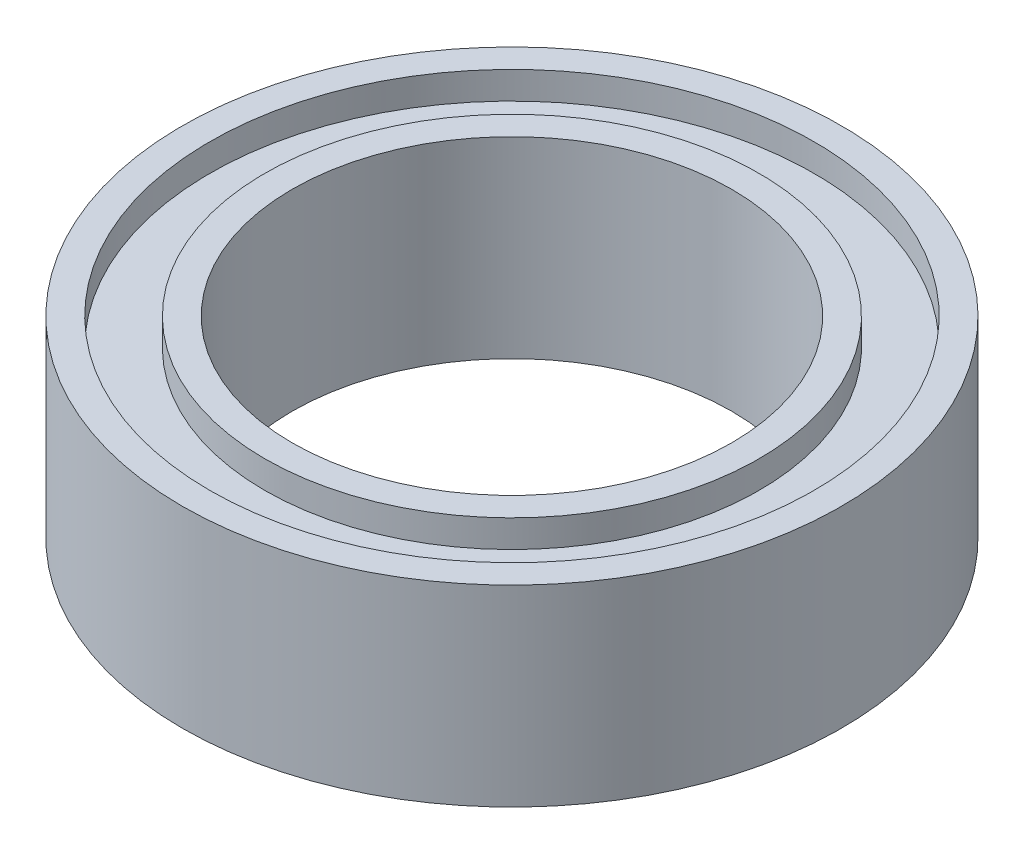
SolidWorks part; units mm, degrees
ref_plane "前视基准面" through (0, 0, 0) normal (0, 0, 1) x (1, 0, 0)
ref_plane "上视基准面" through (0, 0, 0) normal (0, 1, 0) x (1, 0, 0)
ref_plane "右视基准面" through (0, 0, 0) normal (1, 0, 0) x (0, 0, -1)
sketch "草图1" plane through (0, 0, 0) normal (0, 1, 0) x (1, 0, 0)
  circle A0 centre (0, 0) radius 4
  circle A1 centre (0, 0) radius 4.5
  circle A2 centre (0, 0) radius 5.5
  circle A3 centre (0, 0) radius 6
  dimension "D1" = 8
  dimension "D2" = 9
  dimension "D3" = 11
  dimension "D4" = 12
extrude "凸台-拉伸1" add sketch "草图1" along normal blind 3.5 contours A0 | A1
extrude "凸台-拉伸2" add sketch "草图1<3>" along normal blind 3 contours A1 | A2
sketch "草图1<3>" plane through (0, 0, 0) normal (0, 1, 0) x (1, 0, 0) same geometry as "草图1"
extrude "凸台-拉伸3" add sketch "草图1<4>" along normal blind 3.5 contours A2 | A3
sketch "草图1<4>" plane through (0, 0, 0) normal (0, 1, 0) x (1, 0, 0) same geometry as "草图1"
extrude "切除-拉伸1" cut sketch "草图1<5>" along normal blind 0.5 contours A2 | A1
sketch "草图1<5>" plane through (0, 0, 0) normal (0, 1, 0) x (1, 0, 0) same geometry as "草图1"
